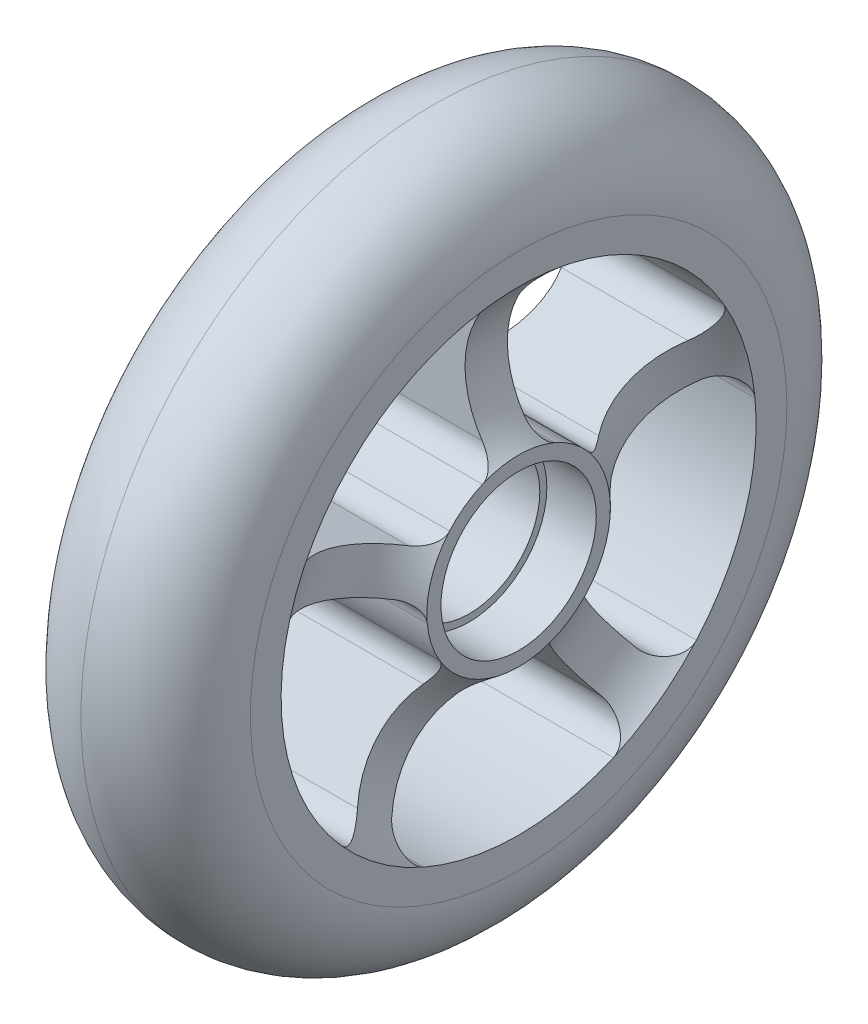
SolidWorks part; units mm, degrees
material "1100-H16 Çubuk (SS)"
ref_plane "Ön Düzlem" through (0, 0, 0) normal (0, 0, 1) x (1, 0, 0)
ref_plane "Üst Düzlem" through (0, 0, 0) normal (0, 1, 0) x (1, 0, 0)
ref_plane "Sağ Düzlem" through (0, 0, 0) normal (1, 0, 0) x (0, 0, -1)
sketch "Çizim1" plane through (0, 0, 0) normal (1, 0, 0) x (0, 0, -1)
  line L0 (139.8333, 413.5) -> (699.1667, 413.5) construction
  line L1 (0, 13) -> (0, 33.6412) construction
  line L2 (3, 12.6491) -> (3, 33.5072)
  line L3 (-3, 12.6491) -> (-3, 33.5072)
  line L4 (-3, 13) -> (-3, 33.6412) construction
  line L5 (3, 13) -> (3, 33.6412) construction
  line L6 (11.103, 6.762) -> (30.9402, 13.2075)
  line L7 (12.9571, 1.0556) -> (32.7943, 7.5011)
  line L8 (9.862, -8.47) -> (22.1221, -25.3445)
  line L9 (5.0079, -11.9967) -> (17.268, -28.8712)
  line L10 (-5.0079, -11.9967) -> (-17.268, -28.8712)
  line L11 (-9.862, -8.47) -> (-22.1221, -25.3445)
  line L12 (-12.9571, 1.0556) -> (-32.7943, 7.5011)
  line L13 (-11.103, 6.762) -> (-30.9402, 13.2075)
  circle A0 centre (0, 0) radius 49.9994
  circle A1 centre (0, 0) radius 36.1412
  circle A2 centre (0, 0) radius 11
  arc A3 (-12.9571, 1.0556) -> (-9.862, -8.47) centre (0, 0) ccw
  arc A4 (-32.7943, 7.5011) -> (-22.1221, -25.3445) centre (0, 0) ccw
  circle A5 centre (0, 0) radius 33.6412 construction
  arc A6 (-5.0079, -11.9967) -> (5.0079, -11.9967) centre (0, 0) ccw
  arc A7 (-17.268, -28.8712) -> (17.268, -28.8712) centre (0, 0) ccw
  arc A8 (22.1221, -25.3445) -> (32.7943, 7.5011) centre (0, 0) ccw
  arc A9 (30.9402, 13.2075) -> (3, 33.5072) centre (0, 0) ccw
  arc A10 (-3, 33.5072) -> (-30.9402, 13.2075) centre (0, 0) ccw
  arc A11 (9.862, -8.47) -> (12.9571, 1.0556) centre (0, 0) ccw
  arc A12 (11.103, 6.762) -> (3, 12.6491) centre (0, 0) ccw
  arc A13 (-3, 12.6491) -> (-11.103, 6.762) centre (0, 0) ccw
  point P37 (0, 0)
  dimension "D1" = 26
  dimension "D2" = 2.5
  dimension "D6" = 99.9988
  dimension "D7" = 72.2825
  dimension "D8" = 22
  dimension "D3" = 3
  dimension "D4" = 3
  dimension "D5" = 5
extrude "Yükseklik-Ekstrüzyon1" add sketch "Çizim1" along normal blind 24 contours A1 L6 A12 L2 A9 A2 A4 L12 A3 L11 A7 L10 A6 L9 L8 A11 L7 A8 L3 A13 L13 A10 | A0 A1 region at (0, 0, 48.5852) region at (0, 0, 35.119)
fillet "Radyus1" radius 3.5 20 edges at (12, 1.0556, 12.9571) (12, 7.5011, 32.7943) (12, -25.3445, 22.1221) (12, -8.47, 9.862) (12, -28.8712, 17.268) (12, -11.9967, 5.0079) (12, -28.8712, -17.268) (12, -11.9967, -5.0079) (12, -8.47, -9.862) (12, -25.3445, -22.1221) (12, 1.0556, -12.9571) (12, 7.5011, -32.7943) (12, 12.6491, -3) (12, 13.2075, -30.9402) (12, 33.5072, -3) (12, 6.762, -11.103) (12, 6.762, 11.103) (12, 12.6491, 3) (12, 33.5072, 3) (12, 13.2075, 30.9402)
sketch "Çizim3" plane through (0, 0, 0) normal (0, 0, 1) x (1, 0, 0)
  line L0 (-73.2942, 0) -> (90.9531, 0) construction
  line L1 (24, -33.6412) -> (0, -33.6412)
  line L2 (24, -33.6412) -> (0, -33.6412) construction
  line L3 (0, -49.9994) -> (0, -33.6412)
  line L4 (0, -13) -> (0, -11)
  line L5 (0, 12) -> (0, 49.9994)
  line L6 (0, -13) -> (24, -13) construction
  line L7 (0, -13) -> (0, -11) construction
  line L8 (0, -13) -> (0, -33.6412)
  line L9 (24, -33.6412) -> (24, -13)
  arc A0 (0, -13) -> (0, -33.6412) centre (-9.8267, -23.3206) cw
  arc A1 (24, -13) -> (24, -33.6412) centre (33.2938, -23.3206) ccw
revolve "Kes-Döndür4" cut sketch "Çizim3" angle 360 about L0
fillet "Radyus2" radius 12 2 edges at (24, 0, -49.9994) (0, 0, -49.9994)
ref_plane "Düzlem1" through (12, 0, 0) normal (1, 0, 0) x (0, 0, -1)
sketch "Çizim4" plane through (12, 0, 0) normal (1, 0, 0) x (0, 0, -1)
  circle A0 centre (0, 0) radius 10
  circle A1 centre (0, 0) radius 11 construction
  circle A2 centre (0, 0) radius 11
  dimension "D1" = 20
extrude "Yükseklik-Ekstrüzyon2" add sketch "Çizim4" along normal offset from surface 7 and the other way offset from surface 7 separate body up to face at (24, 0, 0) other way up to face at (0, 0, 0)
